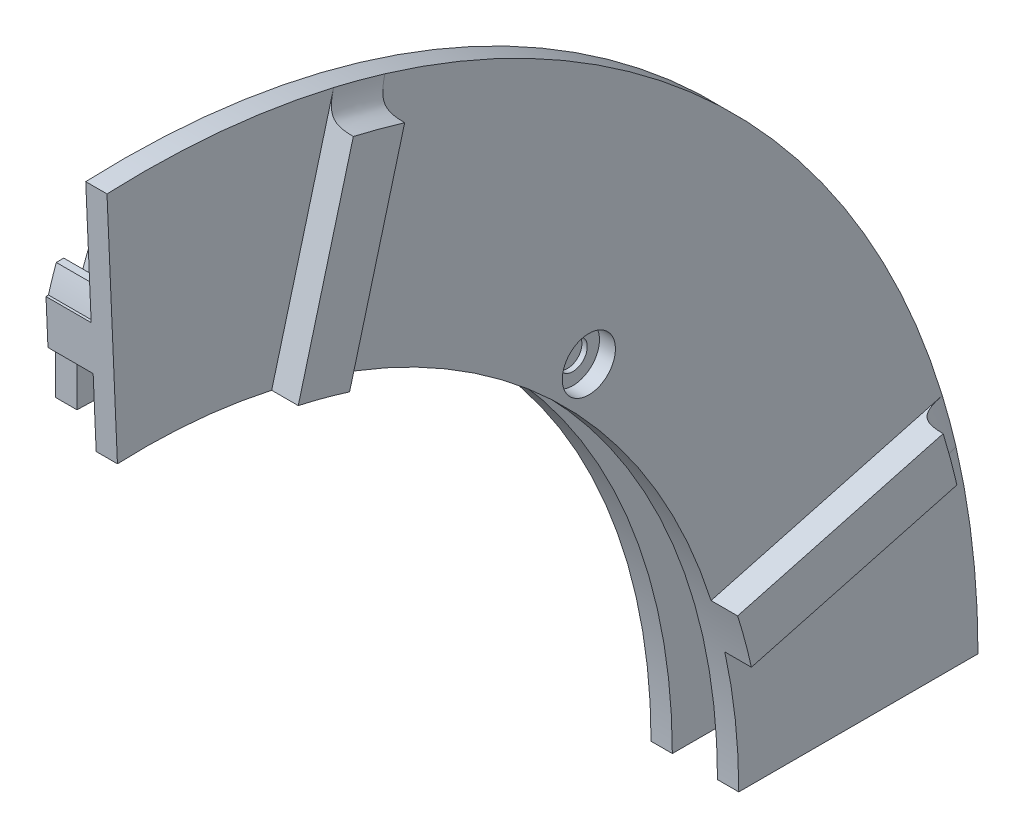
SolidWorks part; units mm, degrees
ref_plane "Plane1" through (0, 0, 0) normal (0, 0, 1) x (1, 0, 0)
ref_plane "Plane2" through (0, 0, 0) normal (0, 1, 0) x (1, 0, 0)
ref_plane "Plane3" through (0, 0, 0) normal (1, 0, 0) x (0, 0, -1)
sketch "HoldingSke" plane through (0, 0, 0) normal (0, 1, 0) x (1, 0, 0)
  line L0 (0, 0) -> (-0.3597, -0.3473)
  line L1 (-15, 0) -> (100, 0) construction
  line L2 (0, 0) -> (-2.1039, 2.3779)
  line L3 (0, 0) -> (-11.863, 4.5341)
  line L4 (0, 0) -> (-6.2122, 5.9991)
  line L5 (0, 0) -> (-46.8476, -17.4728)
  line L6 (0, 0) -> (-7.0462, -4.7541)
  line L7 (-2.1039, 2.3779) -> (8.6586, 51.2059)
  line L8 (-76.2, 54.61) -> (-76.1, 54.61)
  line L9 (-71.009, 38.7566) -> (-53.1078, 45.2721)
  line L10 (-76.2, 71.12) -> (104.1128, 71.12)
  line L11 (0, 0) -> (-8.5, 0)
  line L12 (-76.2, 101.6) -> (-76.133, 101.6)
  line L13 (24.9733, 27.94) -> (52.9518, 28.4284)
  line L14 (24.9733, 27.94) -> (24.9743, 27.94)
  line L15 (24.9733, 27.94) -> (100.4006, 29.5858)
  line L16 (-63.627, -2) -> (-12.827, -2)
  circle A0 centre (0, 0) radius 0.1
  circle A1 centre (0, 0) radius 37.5
  circle A2 centre (0, 0) radius 37.5
  circle A3 centre (0, 0) radius 0.1
  dimension "MHD" = 75
  dimension "Hub_dia" = 75
  dimension "Bore" = 0.2
  dimension "MBD" = 0.2
  dimension "Num_teeth" = 136
  dimension "Pitch" = 0.5
  dimension "Overall_len" = 50
  dimension "Show_teeth" = 136
  dimension "Thickness" = 8.5
  dimension "OAL" = 50.0001
  dimension "T_dim" = 0.1
  dimension "Ap" = 20
  dimension "H" = 19.05
  dimension "Pitch_radius" = 180.3128
  dimension "Width" = 8.5
  dimension "Backlash" = 0.067
  dimension "Addendum_fac" = 1
  dimension "Dedendum_fac" = 1.25
  dimension "Clearance_fac" = 0.25
  dimension "Dedendum_add" = 0.001
  dimension "Module" = 2
sketch "BasProSke" plane through (0, 0, 0) normal (0, 1, 0) x (1, 0, 0)
  line L0 (-10, 0) -> (60, 0) construction
  line L1 (0, 0) -> (0, 138)
  line L2 (0, 0) -> (8.5, 0)
  line L3 (8.5, 0) -> (8.5, 138)
  line L4 (8.5, 138) -> (0, 138)
  dimension "Thickness" = 8.5
  dimension "Diameter" = 276
revolve "Base-Revolve" add sketch "BasProSke" angle 360 about L0
sketch "TooCutSke" plane through (0, 0, 0) normal (1, 0, 0) x (0, 0, -1)
  line L1 (0, 0) -> (0, 107) construction
  line L2 (0, 0) -> (-1.688, 135.9895) construction
  line L3 (0, 0) -> (-6.2823, 271.9119) construction
  line L4 (-1.688, 135.9895) -> (-3.1411, 135.956) construction
  arc A0 (0.8016, 133.4966) -> (-0.8016, 133.4966) centre (0, 0) ccw
  arc A1 (2.5059, 138.0026) -> (-2.5059, 138.0026) centre (0, 0) ccw
  circle A2 centre (0, 0) radius 136 construction
  circle A3 centre (0, 0) radius 127.7982 construction
  arc A4 (-0.8016, 133.4966) -> (-2.5059, 138.0026) centre (-52.4858, 116.523) ccw
  arc A5 (2.5059, 138.0026) -> (0.8016, 133.4966) centre (52.4858, 116.523) ccw
  dimension "Root_dia" = 266.998
  dimension "Overcut_dia" = 276.0508
  dimension "Pitch_dia" = 272
  dimension "Base_dia" = 255.5964
  dimension "Flank_rad" = 54.4
  dimension "Half_ang" = 1.324
  dimension "Half_CT" = 1.4535
extrude "ToothCut" cut sketch "TooCutSke" along normal through all
fillet "Breaks" [suppressed] radius 0.04 tangent propagation no
fillet "RootFillets" [suppressed] radius 0.501
pattern_circular "TeethCuts" count 136 every 2.647 about axis through (-10, 0, 0) along (1, 0, 0) of "ToothCut", "RootFillets", "Breaks"
sketch "HubNeaOneSke" plane through (0, 0, 0) normal (-1, 0, 0) x (0, 0, 1)
  circle A0 centre (0, 0) radius 37.5
  dimension "Diameter" = 75
extrude "HubNearOne" [suppressed] add sketch "HubNeaOneSke" along normal blind 41.5001
sketch "HubNeaBotSke" plane through (0, 0, 0) normal (-1, 0, 0) x (0, 0, 1)
  circle A0 centre (0, 0) radius 37.5
  dimension "Diameter" = 75
extrude "HubNearBoth" [suppressed] add sketch "HubNeaBotSke" along normal blind 20.75
ref_plane "FarPln" through (8.5, 0, 0) normal (1, 0, 0) x (0, 0, -1)
sketch "HubFarSke" plane through (8.5, 0, 0) normal (1, 0, 0) x (0, 0, -1)
  circle A0 centre (0, 0) radius 37.5
  dimension "Diameter" = 75
extrude "HubFar" [suppressed] add sketch "HubFarSke" along normal blind 20.75
sketch "BorSke" plane through (0, 0, 0) normal (1, 0, 0) x (0, 0, -1)
  circle A0 centre (0, 0) radius 0.1
  dimension "Diameter" = 0.2
extrude "Bore" cut sketch "BorSke" along normal mid plane 100.0001
sketch "KeySke" plane through (0, 0, 0) normal (1, 0, 0) x (0, 0, -1)
  line L0 (-0.05, 0) -> (-0.05, 0.2)
  line L1 (-0.05, 0.2) -> (0.05, 0.2)
  line L2 (0.05, 0.2) -> (0.05, 0)
  line L3 (0, 0) -> (0, 34) construction
  line L4 (-0.05, 0) -> (0.05, 0)
  dimension "Offset" = 0.2
  dimension "Width" = 0.1
extrude "Keyway" [suppressed] cut sketch "KeySke" along normal mid plane 100.0001
pattern_circular "Keyway2" [suppressed] count 2 every 90 about axis through (-10, 0, 0) along (1, 0, 0)
sketch "Schizzo1" plane through (8.5, 0, 0) normal (1, 0, 0) x (0, 0, -1)
  line L0 (-5.4524, 124.881) -> (-6.1067, 139.8668)
  line L1 (125, 0) -> (140, 0)
  line L2 (0, 0) -> (125, 0) construction
  line L3 (0, 0) -> (-5.4524, 124.881) construction
  arc A0 (-6.1067, 139.8668) -> (140, 0) centre (0, 0) ccw
  arc A1 (125, 0) -> (-5.4524, 124.881) centre (0, 0) ccw
  dimension "D1" = 280
  dimension "D2" = 250
  dimension "D3" = 92.5
extrude "Taglio-Estrusione1" cut sketch "Schizzo1" against normal blind 10
sketch "Schizzo2" plane through (8.5, 0, 0) normal (1, 0, 0) x (0, 0, -1)
  line L0 (-6.8482, 156.8506) -> (-4.8854, 111.8934)
  line L1 (157, 0) -> (112, 0)
  line L2 (-4.8854, 111.8934) -> (0, 0) construction
  line L3 (0, 0) -> (112, 0) construction
  arc A0 (157, 0) -> (-6.8482, 156.8506) centre (0, 0) ccw
  arc A1 (112, 0) -> (-4.8854, 111.8934) centre (0, 0) ccw
  dimension "D1" = 224
  dimension "D2" = 45
  dimension "D3" = 92.5
extrude "Estrusione-Estrusione1" add sketch "Schizzo2" along normal blind 4
sketch "Schizzo3" plane through (0, 0, 0) normal (-1, 0, 0) x (0, 0, 1)
  line L2 (-130, 0) -> (-112, 0)
  line L3 (0, 130) -> (0, 112)
  arc A2 (0, 112) -> (-112, 0) centre (0, 0) ccw
  arc A3 (0, 130) -> (-130, 0) centre (0, 0) ccw
  dimension "D1" = 224
  dimension "D2" = 18
extrude "Estrusione-Estrusione2" add sketch "Schizzo3" along normal blind 4
chamfer "Smusso2" distance 4 angle 45 1 edges at (-4, 91.9239, -91.9239)
sketch "Schizzo4" plane through (12.5, 0, 0) normal (1, 0, 0) x (0, 0, -1)
  line L0 (0, 0) -> (83.7922, 83.7922) construction
  line L2 (0, 0) -> (138, 0) construction
  arc A0 (112, 0) -> (-4.8854, 111.8934) centre (0, 0) ccw construction
  point P0 (83.7922, 83.7922)
  dimension "D1" = 45
  dimension "D2" = 118.5
hole_wizard "Foro lamato per Bullone M12 a testa esagonale (Classe superiore)-1" positions "Schizzo4" profile "Schizzo5" counterbore size "M12" standard "DIN"
sketch "Schizzo5" plane through (12.5, 83.7922, -83.7922) normal (0, 1, 0) x (0, 0, -1)
  line L0 (0, 0) -> (0, 19.7223)
  line L1 (0, 19.7223) -> (2.7, 18.1)
  line L2 (2.7, 18.1) -> (2.7, 3)
  line L3 (2.7, 3) -> (5, 3)
  line L4 (5, 3) -> (5, 0)
  line L5 (5, 0) -> (0, 0)
  line L10 (0, 19.7223) -> (-2.7, 18.1) construction
  line L11 (0, -6.35) -> (0, 107.95) construction
  dimension "Hole Dia." = 5.4
  dimension "Hole Depth" = 18.1
  dimension "C'Bore Dia." = 10
  dimension "C'Bore Depth" = 3
  dimension "Drill Angle" = 118
sketch "Schizzo6" plane through (12.5, 0, 0) normal (1, 0, 0) x (0, 0, -1)
  line L0 (0, 0) -> (39.3405, 146.8207) construction
  line L1 (0, 0) -> (146.8207, 39.3405) construction
  line L3 (0, 0) -> (157, 0) construction
  line L4 (24.1292, 109.3699) -> (34.4896, 148.0354)
  line L5 (33.7885, 106.7817) -> (44.1488, 145.4472)
  line L6 (109.3699, 24.1292) -> (148.0354, 34.4896)
  line L7 (106.7817, 33.7885) -> (145.4472, 44.1488)
  arc A0 (157, 0) -> (-6.8482, 156.8506) centre (0, 0) ccw construction
  arc A6 (109.3699, 24.1292) -> (106.7817, 33.7885) centre (0, 0) ccw
  arc A7 (33.7885, 106.7817) -> (24.1292, 109.3699) centre (0, 0) ccw
  arc A8 (112, 0) -> (-4.8854, 111.8934) centre (0, 0) ccw construction
  arc A9 (148.0354, 34.4896) -> (145.4472, 44.1488) centre (0, 0) ccw
  arc A10 (44.1488, 145.4472) -> (34.4896, 148.0354) centre (0, 0) ccw
  dimension "D7" = 5
  dimension "D1" = 60
  dimension "D2" = 15
  dimension "D3" = 10
  dimension "D4" = 5
  dimension "D5" = 5
  dimension "D6" = 10
extrude "Estrusione-Estrusione3" add sketch "Schizzo6" along normal blind 5
fillet "Raccordo1" radius 5 2 edges at (12.5, 146.8207, -39.3405) (12.5, 39.3405, -146.8207) conic rho 0.6
equation "' \"Module@HoldingSke\" = 6.35"
equation "' \"Num_teeth@HoldingSke\" = 12"
equation "' \"Ap@HoldingSke\" =  20"
equation "' \"Ap@HoldingSke\" = 20"
equation "' \"Width@HoldingSke\" = 0.5 * 25.4"
equation "' \"Hub_dia@HoldingSke\"= 1 * 25.4"
equation "' \"Hub_dia@HoldingSke\" = 1 * 25.4"
equation "' \"Overall_len@HoldingSke\" = 1.0 * 25.4"
equation "' \"Bore@HoldingSke\" = 0.75 * 25.4"
equation "' \"T_dim@HoldingSke\" = 0.1 * 25.4"
equation "' \"Width@KeySke\" = 0.25 * 25.4"
equation "' \"Show_teeth@HoldingSke\" = 13"
equation "' \"Backlash@HoldingSke\" = 0.009 * 25.4"
equation "' \"Addendum_fac@HoldingSke\" = 1.0"
equation "' \"Dedendum_fac@HoldingSke\" = 1.25"
equation "' \"Dedendum_add@HoldingSke\" = 0.00005 * 25.4"
equation "' \"Clearance_fac@HoldingSke\" = 0.25"
equation "\"Pitch@HoldingSke\" = 1 / \"Module@HoldingSke\""
equation "\"Overcut_dia@TooCutSke\" = (\"Num_teeth@HoldingSke\" + 2 * \"Addendum_fac@HoldingSke\") / \"Pitch@HoldingSke\" + 0.002 * 25.4"
equation "\"Pitch_dia@TooCutSke\" = \"Num_teeth@HoldingSke\" / \"Pitch@HoldingSke\""
equation "\"Base_dia@TooCutSke\" = \"Num_teeth@HoldingSke\" / \"Pitch@HoldingSke\" * cos((\"Ap@HoldingSke\"  * 3.14159265 / 180))"
equation "\"Root_dia@TooCutSke\" = (\"Num_teeth@HoldingSke\" + 2) / \"Pitch@HoldingSke\" - 2 * (\"Addendum_fac@HoldingSke\" + \"Dedendum_fac@HoldingSke\") / \"Pitch@HoldingSke\" - \"Dedendum_add@HoldingSke\" * 2"
equation "\"Half_ang@TooCutSke\" = 180 / \"Num_teeth@HoldingSke\""
equation "\"Half_CT@TooCutSke\" = \"Num_teeth@HoldingSke\" / \"Pitch@HoldingSke\" * sin((3.14159265 / 2 / \"Num_teeth@HoldingSke\")) / 2 - 7 * \"Backlash@HoldingSke\" / 4"
equation "\"Flank_rad@TooCutSke\" = \"Num_teeth@HoldingSke\" / \"Pitch@HoldingSke\" / 5"
equation "\"Radius@RootFillets\" = \"Clearance_fac@HoldingSke\" / \"Pitch@HoldingSke\" + \"Dedendum_add@HoldingSke\""
equation "\"Break_rad@Breaks\" = 0.02 / \"Pitch@HoldingSke\""
equation "\"Thickness@HoldingSke\" = \"Width@HoldingSke\""
equation "\"OAL@HoldingSke\" = \"Thickness@HoldingSke\""
equation "\"MHD@HoldingSke\" = (\"Num_teeth@HoldingSke\" + 2) / \"Pitch@HoldingSke\" - 2 * (\"Addendum_fac@HoldingSke\" + \"Dedendum_fac@HoldingSke\")  / \"Pitch@HoldingSke\" - \"Dedendum_add@HoldingSke\" * 2"
equation "\"MBD@HoldingSke\" = (\"Num_teeth@HoldingSke\" + 2) / \"Pitch@HoldingSke\" - 2 * (\"Addendum_fac@HoldingSke\" + \"Dedendum_fac@HoldingSke\")  / \"Pitch@HoldingSke\" - \"Dedendum_add@HoldingSke\" * 2 - 0.002 * 25.4"
equation "\"MHD@HoldingSke\" = ((sgn( \"MHD@HoldingSke\" - \"Hub_dia@HoldingSke\" )-1)*( \"MHD@HoldingSke\" - \"Hub_dia@HoldingSke\" ))/-2+ \"Hub_dia@HoldingSke\""
equation "\"MBD@HoldingSke\" = ((sgn( \"MBD@HoldingSke\" - \"Bore@HoldingSke\" )-1)*( \"MBD@HoldingSke\" - \"Bore@HoldingSke\" ))/-2+ \"Bore@HoldingSke\""
equation "\"OAL@HoldingSke\" = ((sgn( \"OAL@HoldingSke\" - \"Overall_len@HoldingSke\" )+1)*( \"OAL@HoldingSke\" - \"Overall_len@HoldingSke\" ))/2 + \"Overall_len@HoldingSke\" + 0.000002 * 25.4"
equation "\"Num_teeth@TeethCuts\" = int( \"Show_teeth@HoldingSke\" ) + 1"
equation "\"Num_teeth@TeethCuts\" = ((sgn( \"Num_teeth@TeethCuts\" - \"Num_teeth@HoldingSke\" )-1)*( \"Num_teeth@TeethCuts\" - \"Num_teeth@HoldingSke\" ))/-2+ \"Num_teeth@HoldingSke\""
equation "\"Num_teeth@TeethCuts\" = ((sgn( \"Num_teeth@TeethCuts\" - 2.0)+1)*( \"Num_teeth@TeethCuts\" - 2.0))/2 +2.0"
equation "\"Angle@TeethCuts\" = 360.0 / \"Num_teeth@HoldingSke\""
equation "\"Diameter@BasProSke\" = (\"Num_teeth@HoldingSke\" + 2 * \"Addendum_fac@HoldingSke\") / \"Pitch@HoldingSke\""
equation "\"Thickness@BasProSke\"  = \"Thickness@HoldingSke\""
equation "' \"Fillet_rad@BasProSke\" =  \"Thickness@HoldingSke\" * 0.05"
equation "' \"Fillet_rad@BasProSke\" = \"Thickness@HoldingSke\" * 0.05"
equation "\"MHD@HoldingSke\" = ((sgn( \"MHD@HoldingSke\" - \"Root_dia@TooCutSke\" )-1)*( \"MHD@HoldingSke\" - \"Root_dia@TooCutSke\" ))/-2+ \"Root_dia@TooCutSke\""
equation "\"Diameter@HubNeaOneSke\" = \"MHD@HoldingSke\""
equation "\"Length@HubNearOne\" = \"OAL@HoldingSke\" - \"Thickness@BasProSke\""
equation "\"Diameter@HubNeaBotSke\" = \"MHD@HoldingSke\""
equation "\"Length@HubNearBoth\" = ( \"OAL@HoldingSke\" - \"Thickness@BasProSke\" ) / 2.0"
equation "\"Thickness@FarPln\" = \"Thickness@BasProSke\""
equation "\"Diameter@HubFarSke\" = \"MHD@HoldingSke\""
equation "\"Length@HubFar\" = ( \"OAL@HoldingSke\" - \"Thickness@BasProSke\" ) / 2.0"
equation "\"Diameter@BorSke\" = \"MBD@HoldingSke\""
equation "\"D1@Bore\" = \"OAL@HoldingSke\" * 2.0"
equation "\"D1@Keyway\" = \"OAL@HoldingSke\" * 2.0"
equation "\"Offset@KeySke\" = \"T_dim@HoldingSke\" + \"MBD@HoldingSke\" / 2.0"
